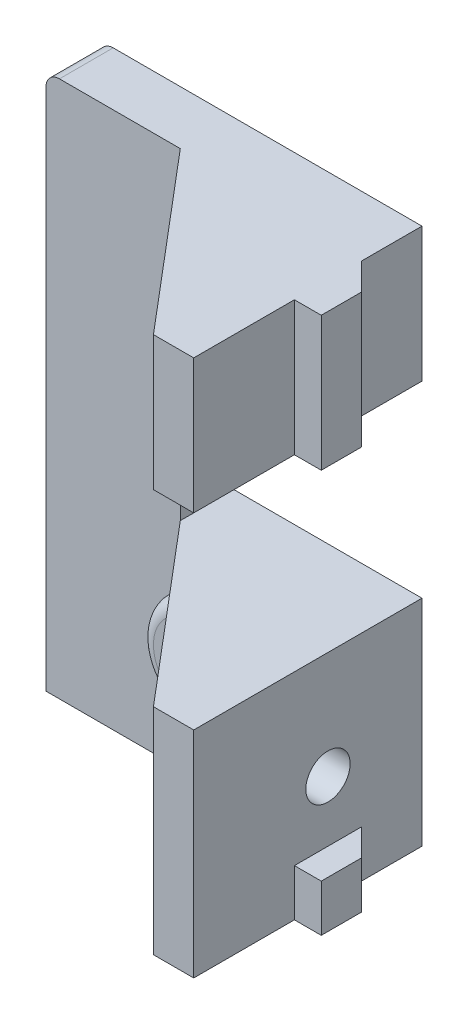
SolidWorks part; units mm, degrees
ref_plane "Front Plane" through (0, 0, 0) normal (0, 0, 1) x (1, 0, 0)
ref_plane "Top Plane" through (0, 0, 0) normal (0, 1, 0) x (1, 0, 0)
ref_plane "Right Plane" through (0, 0, 0) normal (1, 0, 0) x (0, 0, -1)
sketch "Sketch1" plane through (0, 0, 0) normal (0, 0, 1) x (1, 0, 0)
  line L1 (-26.7581, 33.2419) -> (-2.7581, 33.2419)
  line L2 (-26.7581, 33.2419) -> (-26.7581, -6.7581)
  line L3 (-26.7581, -6.7581) -> (-2.7581, -6.7581)
  line L4 (-2.7581, 33.2419) -> (-2.7581, -6.7581)
  dimension "D1" = 40
  dimension "D2" = 24
extrude "Boss-Extrude1" add sketch "Sketch1" along normal blind 4
fillet "Fillet1" radius 1 1 edges at (-26.7581, 33.2419, 2)
sketch "Sketch3" plane through (0, 0, 0) normal (0, 0, -1) x (-1, 0, 0)
  line L0 (2.7581, -6.7581) -> (2.7581, 33.2419) construction
  line L1 (2.7581, 9.2419) -> (16.7581, 9.2419)
  line L2 (2.7581, 9.2419) -> (2.7581, 23.2419)
  line L3 (2.7581, 23.2419) -> (16.7581, 23.2419)
  line L4 (16.7581, 9.2419) -> (16.7581, 23.2419)
  line L5 (26.7581, -6.7581) -> (2.7581, -6.7581) construction
  dimension "D1" = 14
  dimension "D2" = 14
  dimension "D3" = 16
extrude "Cut-Extrude2" cut sketch "Sketch3" against normal through all both and the other way through all
sketch "Sketch5" plane through (0, 0, 4) normal (0, 0, 1) x (1, 0, 0)
  line L0 (-26.7581, -6.7581) -> (-2.7581, -6.7581) construction
  line L1 (-2.7581, 9.2419) -> (-5.7581, 9.2419)
  line L2 (-2.7581, 9.2419) -> (-2.7581, -6.7581)
  line L3 (-2.7581, -6.7581) -> (-5.7581, -6.7581)
  line L4 (-5.7581, 9.2419) -> (-5.7581, -6.7581)
  dimension "D1" = 3
extrude "Boss-Extrude2" add sketch "Sketch5" along normal blind 13
sketch "Sketch6" plane through (0, -6.7581, 0) normal (0, -1, 0) x (1, 0, 0)
  line L0 (-5.7581, 17) -> (-16.6664, 4)
  line L1 (-26.7581, 4) -> (-5.7581, 4) construction
  line L2 (-16.6664, 4) -> (-5.7581, 4)
  line L3 (-5.7581, 4) -> (-5.7581, 17)
extrude "Boss-Extrude3" add sketch "Sketch6" against normal blind 3
sketch "Sketch7" plane through (0, 9.2419, 0) normal (0, 1, 0) x (1, 0, 0)
  line L0 (-5.7581, -17) -> (-16.7581, -4)
  line L1 (-16.7581, -4) -> (-5.7581, -4)
  line L2 (-5.7581, -4) -> (-5.7581, -17)
extrude "Boss-Extrude4" add sketch "Sketch7" against normal blind 3
sketch "Sketch8" plane through (-5.7581, 0, 0) normal (-1, 0, 0) x (0, 0, 1)
  line L0 (17, 6.2419) -> (17, -3.7581) construction
  line L1 (17, -6.7581) -> (4, -6.7581) construction
  circle A0 centre (7, 1.2419) radius 1.65
  dimension "D1" = 3.3
  dimension "D2" = 10
  dimension "D3" = 8
extrude "Cut-Extrude4" cut sketch "Sketch8" against normal blind 3
sketch "Sketch9" plane through (0, 0, 4) normal (0, 0, 1) x (1, 0, 0)
  line L0 (-16.7581, 23.2419) -> (-2.7581, 23.2419) construction
  line L1 (-2.7581, 33.2419) -> (-5.7581, 33.2419)
  line L2 (-2.7581, 33.2419) -> (-2.7581, 23.2419)
  line L3 (-2.7581, 23.2419) -> (-5.7581, 23.2419)
  line L4 (-5.7581, 33.2419) -> (-5.7581, 23.2419)
  dimension "D1" = 3
extrude "Boss-Extrude5" add sketch "Sketch9" along normal blind 13
sketch "Sketch10" plane through (0, 33.2419, 0) normal (0, 1, 0) x (1, 0, 0)
  line L0 (-5.7581, -17) -> (-16.7581, -4)
  line L1 (-16.7581, -4) -> (-5.7581, -4)
  line L2 (-5.7581, -4) -> (-5.7581, -17)
extrude "Boss-Extrude6" add sketch "Sketch10" against normal blind 6
sketch "Sketch11" plane through (-2.7581, 0, 0) normal (1, 0, 0) x (0, 0, -1)
  line L0 (-17, 33.2419) -> (0, 33.2419) construction
  line L1 (-9.5, 33.2419) -> (-4.5, 33.2419)
  line L2 (-9.5, 33.2419) -> (-9.5, 23.2419)
  line L3 (-9.5, 23.2419) -> (-4.5, 23.2419)
  line L4 (-4.5, 33.2419) -> (-4.5, 23.2419)
  line L5 (-17, 23.2419) -> (0, 23.2419) construction
  line L6 (-17, 23.2419) -> (-17, 33.2419) construction
  dimension "D1" = 5
  dimension "D2" = 7.5
extrude "Boss-Extrude7" add sketch "Sketch11" along normal blind 2
chamfer "Chamfer1" distance 2 angle 45 1 edges at (-0.7581, 28.2419, 4.5)
sketch "Sketch12" plane through (0, 0, 0) normal (0, 0, -1) x (-1, 0, 0)
  line L0 (26.7581, -6.7581) -> (2.7581, -6.7581) construction
  line L5 (2.7581, -6.7581) -> (2.7581, 9.2419) construction
  circle A0 centre (14.7581, 1.2419) radius 3.065
  dimension "D1" = 6.13
  dimension "D2" = 8
  dimension "D4" = 12
extrude "Cut-Extrude5" cut sketch "Sketch12" against normal blind 3.1
sketch "Sketch15" plane through (0, 0, 0) normal (0, 0, -1) x (-1, 0, 0)
  line L4 (26.7581, -6.7581) -> (2.7581, -6.7581) construction
  line L6 (16.7581, 23.2419) -> (16.7581, 9.2419) construction
  circle A0 centre (19.7581, 20.2419) radius 1.6
  dimension "D1" = 3.2
  dimension "D2" = 3
  dimension "D3" = 27
extrude "Cut-Extrude6" cut sketch "Sketch15" against normal blind 2.12
sketch "Sketch17" plane through (0, 0, 4) normal (0, 0, 1) x (1, 0, 0)
  circle A1 centre (-14.7581, 1.2419) radius 4
  dimension "D1" = 8
extrude "Boss-Extrude8" add sketch "Sketch17" along normal blind 1
fillet "Fillet3" radius 1 1 edges at (-10.7581, 1.2419, 5)
sketch "Sketch21" plane through (0, 0, 0) normal (0, 0, -1) x (-1, 0, 0)
  circle A0 centre (14.7581, 1.2419) radius 2.25
  dimension "D1" = 4.5
extrude "Boss-Extrude11" add sketch "Sketch21" against normal blind 2.9 separate body contours A0
sketch "Sketch23" plane through (-2.7581, 0, 0) normal (1, 0, 0) x (0, 0, -1)
  line L0 (-17, -6.7581) -> (0, -6.7581) construction
  line L1 (-9.5, -6.7581) -> (-4.5, -6.7581)
  line L2 (-9.5, -6.7581) -> (-9.5, -3.2581)
  line L3 (-9.5, -3.2581) -> (-4.5, -3.2581)
  line L4 (-4.5, -6.7581) -> (-4.5, -3.2581)
  dimension "D1" = 3.5
extrude "Boss-Extrude12" add sketch "Sketch23" along normal blind 2
chamfer "Chamfer2" distance 2 angle 45 1 edges at (-0.7581, -5.0081, 4.5)
fillet "Fillet5" radius 0.5 1 edges at (-21.3581, 20.2419, 0)
